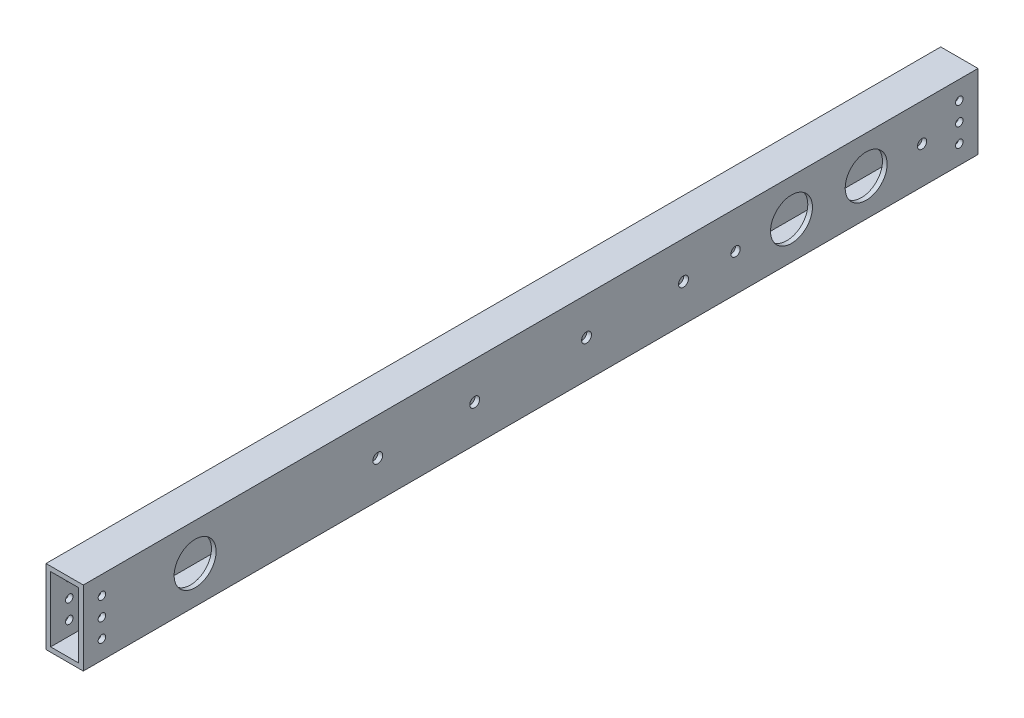
SolidWorks part; units mm, degrees
ref_plane "Front Plane" through (0, 0, 0) normal (0, 0, 1) x (1, 0, 0)
ref_plane "Top Plane" through (0, 0, 0) normal (0, 1, 0) x (1, 0, 0)
ref_plane "Right Plane" through (0, 0, 0) normal (1, 0, 0) x (0, 0, -1)
sketch "Sketch1" plane through (0, 0, 0) normal (0, 0, 1) x (1, 0, 0)
  line L0 (-9.525, 22.225) -> (9.525, 22.225)
  line L1 (-12.7, 25.4) -> (12.7, 25.4)
  line L2 (-12.7, 25.4) -> (-12.7, -25.4)
  line L3 (-12.7, -25.4) -> (12.7, -25.4)
  line L4 (12.7, 25.4) -> (12.7, -25.4)
  line L5 (-12.7, 25.4) -> (12.7, -25.4) construction
  line L6 (-12.7, -25.4) -> (12.7, 25.4) construction
  line L7 (9.525, 22.225) -> (9.525, -22.225)
  line L8 (-9.525, -22.225) -> (9.525, -22.225)
  line L9 (-9.525, 22.225) -> (-9.525, -22.225)
  point P0 (0, 0)
  dimension "D1" = 50.8
  dimension "D2" = 25.4
  dimension "D3" = 3.175
extrude "Boss-Extrude1" add sketch "Sketch1" along normal mid plane 609.6
hole_wizard "#10 Clearance Hole1" positions "Sketch4" profile "Sketch3" hole size "#10" standard "ANSI Inch" end condition through all
sketch "Sketch4" plane through (12.7, 0, 0) normal (1, 0, 0) x (0, 0, -1)
  line L0 (-304.8, 25.4) -> (304.8, 25.4) construction
  line L1 (-304.8, -25.4) -> (-304.8, 25.4) construction
  point P0 (-292.1, 12.7)
  point P13 (-292.1, 0)
  point P14 (-292.1, -12.7)
  dimension "D2" = 12.7
  dimension "D3" = 12.7
  dimension "D1" = 3
sketch "Sketch3" plane through (12.7, 12.7, 292.1) normal (0, 1, 0) x (0, 0, -1)
  line L0 (0, 0) -> (0, 25.4)
  line L1 (0, 25.4) -> (2.5527, 25.4)
  line L2 (2.5527, 25.4) -> (2.5527, 0)
  line L5 (2.5527, 0) -> (0, 0)
  line L11 (0, -6.35) -> (0, 107.95) construction
  dimension "Thru Hole Dia." = 5.1054
  dimension "Thru Hole Depth" = 25.4
mirror "Mirror1" about plane through (0, 0, 0) normal (0, 0, 1) of "#10 Clearance Hole1"
hole_wizard "1/4 Clearance Hole2" positions "Sketch6" profile "Sketch5" hole size "1/4" standard "ANSI Inch" end condition through all
sketch "Sketch6" plane through (12.7, 0, 0) normal (1, 0, 0) x (0, 0, -1)
  line L0 (-38.1, 0) -> (38.1, 0) construction
  point P0 (-38.1, 0)
  point P2 (38.1, 0)
  point P13 (-104.14, 0)
  point P15 (104.14, 0)
  dimension "D1" = 76.2
  dimension "D2" = 66.04
  dimension "D3" = 66.04
sketch "Sketch5" plane through (12.7, 0, 38.1) normal (0, 1, 0) x (0, 0, -1)
  line L0 (0, 0) -> (0, 25.4)
  line L1 (0, 25.4) -> (3.3782, 25.4)
  line L2 (3.3782, 25.4) -> (3.3782, 0)
  line L5 (3.3782, 0) -> (0, 0)
  line L11 (0, -6.35) -> (0, 107.95) construction
  dimension "Thru Hole Dia." = 6.7564
  dimension "Thru Hole Depth" = 25.4
sketch "Sketch7" plane through (12.7, 0, 0) normal (1, 0, 0) x (0, 0, -1)
  line L0 (304.8, -25.4) -> (304.8, 25.4) construction
  line L1 (-304.8, -25.4) -> (-304.8, 25.4) construction
  line L2 (139.6238, 0) -> (266.7, 0) construction
  line L3 (279.4, -25.4) -> (279.4, 25.4) construction
  line L4 (-304.8, -25.4) -> (304.8, -25.4) construction
  line L5 (-304.8, 25.4) -> (304.8, 25.4) construction
  circle A0 centre (-228.6, 0) radius 14.2875
  circle A1 centre (177.7238, 0) radius 14.2875
  circle A2 centre (228.6, 0) radius 14.2875
  circle A3 centre (177.7238, 0) radius 26.67 construction
  circle A4 centre (228.6, 0) radius 26.67 construction
  circle A5 centre (139.6238, 0) radius 3.175
  circle A6 centre (266.7, 0) radius 3.175
  circle A7 centre (139.6238, 0) radius 6.35 construction
  dimension "D1" = 28.575
  dimension "D2" = 28.575
  dimension "D7" = 53.34
  dimension "D8" = 6.35
  dimension "D12" = 12.7
  dimension "D3" = 50.8762
  dimension "D4" = 76.2
  dimension "D5" = 76.2
  dimension "D6" = 406.3238
  dimension "D9" = 38.1
  dimension "D10" = 38.1
  dimension "D11" = 127.0762
  dimension "D13" = 25.4
extrude "Cut-Extrude1" cut sketch "Sketch7" against normal through all
